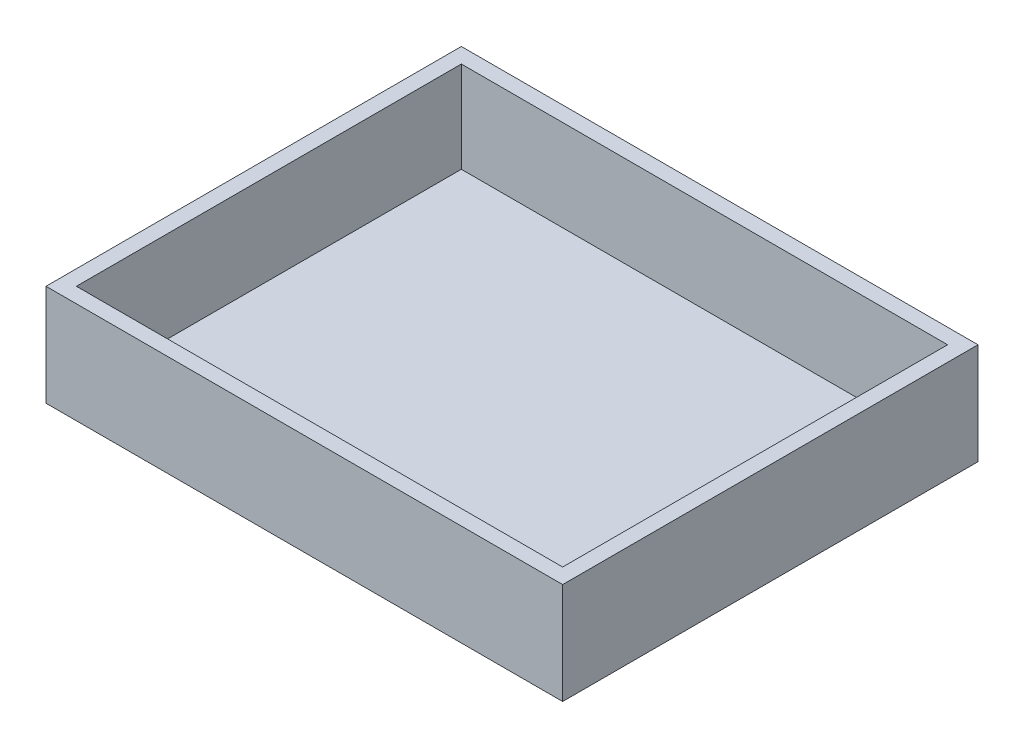
SolidWorks part; units mm, degrees
note: The reader was unsure of these and kept them because the rebuilt part matched: shared geometry of "Sketch1<3>".
ref_plane "Front Plane" through (0, 0, 0) normal (0, 0, 1) x (1, 0, 0)
ref_plane "Top Plane" through (0, 0, 0) normal (0, 1, 0) x (1, 0, 0)
ref_plane "Right Plane" through (0, 0, 0) normal (1, 0, 0) x (0, 0, -1)
sketch "Sketch1" plane through (0, 0, 0) normal (0, 1, 0) x (1, 0, 0)
  line L0 (-25.5, 20.5) -> (25.5, 20.5)
  line L1 (-24, 19) -> (24, 19)
  line L2 (-24, 19) -> (-24, -19)
  line L3 (-24, -19) -> (24, -19)
  line L4 (24, 19) -> (24, -19)
  line L5 (-24, 19) -> (24, -19) construction
  line L6 (-24, -19) -> (24, 19) construction
  line L7 (25.5, 20.5) -> (25.5, -20.5)
  line L8 (-25.5, -20.5) -> (25.5, -20.5)
  line L9 (-25.5, 20.5) -> (-25.5, -20.5)
  point P0 (0, 0)
  dimension "D1" = 48
  dimension "D2" = 38
  dimension "D3" = 1.5
extrude "Boss-Extrude1" add sketch "Sketch1" along normal blind 1 contours L0 L9 L8 L7 L1 L4 L3 L2 | L4 L1 L2 L3
extrude "Boss-Extrude2" add sketch "Sketch1<3>" along normal blind 10 contours L8 L7 L0 L9
sketch "Sketch1<3>" plane through (0, 0, 0) normal (0, 1, 0) x (1, 0, 0) same geometry as "Sketch1"
sketch "Sketch2" plane through (0, 10, 0) normal (0, 1, 0) x (1, 0, 0)
  line L0 (25.5, -20.5) -> (25.5, 20.5) construction
  line L1 (24, 19) -> (25.5, 19)
  line L2 (24, 19) -> (24, 7.639)
  line L3 (24, 7.639) -> (25.5, 7.639)
  line L4 (25.5, 19) -> (25.5, 7.639)
  line L5 (-25.5, 20.5) -> (-25.5, -20.5) construction
  line L6 (24, -19) -> (25.5, -19)
  line L7 (24, -19) -> (24, -7.5194)
  line L8 (24, -7.5194) -> (25.5, -7.5194)
  line L9 (25.5, -19) -> (25.5, -7.5194)
  line L10 (-24, 19) -> (-25.5, 19)
  line L11 (-24, 19) -> (-24, 8.0362)
  line L12 (-24, 8.0362) -> (-25.5, 8.0362)
  line L13 (-25.5, 19) -> (-25.5, 8.0362)
  line L15 (-24, -19) -> (-25.5, -19)
  line L16 (-24, -19) -> (-24, -8.1848)
  line L17 (-24, -8.1848) -> (-25.5, -8.1848)
  line L18 (-25.5, -19) -> (-25.5, -8.1848)
